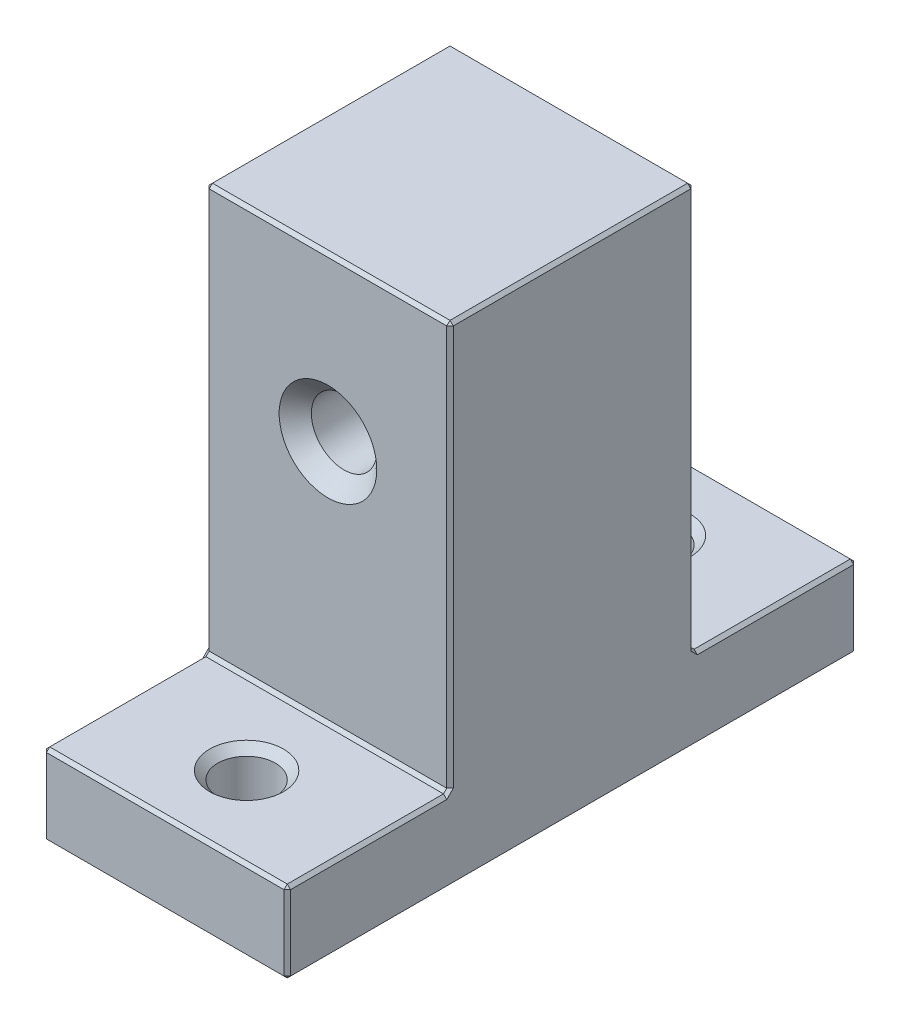
SolidWorks part; units mm, degrees
note: '?' marks a value the reader was unsure of. The reader was unsure of these and kept them because the rebuilt part matched: shared geometry of "Sketch1<3>".
material "6061-T6 (SS)"
ref_plane "Front Plane" through (0, 0, 0) normal (0, 0, 1) x (1, 0, 0)
ref_plane "Top Plane" through (0, 0, 0) normal (0, 1, 0) x (1, 0, 0)
ref_plane "Right Plane" through (0, 0, 0) normal (1, 0, 0) x (0, 0, -1)
ref_axis "X Axis" through (88.99, 0, 0) along (-1, 0, 0)?
ref_axis "Y Axis" through (0, 55, 0) along (0, -1, 0)?
ref_axis "Z Axis" through (0, 0, -88.99) along (0, 0, 1)?
sketch "Sketch1" plane through (0, 0, 0) normal (0, 1, 0) x (1, 0, 0)
  line L5 (-9.525, -22.225) -> (9.525, -22.225)
  line L6 (-9.525, -22.225) -> (-9.525, 22.225)
  line L11 (-9.525, 22.225) -> (9.525, 22.225)
  line L12 (9.525, -22.225) -> (9.525, 22.225)
  line L13 (0, 22.225) -> (0, -22.225) construction
  line L14 (-9.525, 0) -> (9.525, 0) construction
  line L15 (-9.525, -9.525) -> (9.525, -9.525)
  line L16 (-9.525, -9.525) -> (-9.525, 9.525)
  line L17 (-9.525, 9.525) -> (9.525, 9.525)
  line L18 (9.525, -9.525) -> (9.525, 9.525)
  line L19 (0, 9.525) -> (0, -9.525) construction
  line L20 (-9.525, 0) -> (9.525, 0) construction
  point P0 (0, 0)
  point P4 (0, 0)
  dimension "D1" = 19.05
  dimension "D2" = 19.05
  dimension "D3" = 44.45
extrude "Boss-Extrude1" add sketch "Sketch1" along normal blind 6.35 contours L5 L16 L11 L6 | L5 L18 L11 L16 | L18 L5 L12 L11
extrude "Boss-Extrude2" add sketch "Sketch1<3>" along normal blind 38.1 contours L5 L18 L11 L16
sketch "Sketch1<3>" plane through (0, 0, 0) normal (0, 1, 0) x (1, 0, 0) same geometry as "Sketch1"
sketch "Sketch3" plane through (0, 0, 9.525) normal (0, 0, 1) x (1, 0, 0)
  line L0 (0, 0) -> (0, 25.4) construction
  point P1 (0, 25.4)
  point P13 (0, 25.4)
  dimension "D1" = 25.4
hole_wizard "1/4-20 Tapped Hole1" positions "Sketch3" profile "Sketch4" tap size "1/4-20" standard "ANSI Inch" end condition through all
sketch "Sketch4" plane through (0, 25.4, 9.525) normal (1, 0, 0) x (0, -1, 0)
  line L0 (0, 0) -> (0, 19.05)
  line L1 (0, 19.05) -> (3.81, 19.05)
  line L2 (2.5527, 17.7927) -> (2.5527, 1.2573)
  line L3 (2.5527, 1.2573) -> (3.81, 0)
  line L5 (3.81, 0) -> (0, 0)
  line L6 (-2.5527, 1.2573) -> (-3.81, 0) construction
  line L7 (3.81, 19.05) -> (2.5527, 17.7927)
  line L8 (-3.81, 19.05) -> (-2.5527, 17.7927) construction
  line L11 (0, -6.35) -> (0, 107.95) construction
  dimension "Thru Tap Drill Dia." = 5.1054
  dimension "Thru Tap Drill Depth" = 19.05
  dimension "Near C'Sink Dia." = 7.62
  dimension "Near C'Sink Angle" = 90
  dimension "Far C'Sink Dia." = 7.62
  dimension "Far C'Sink Angle" = 90
cosmetic thread "Hole Thread1" parameters "D2"=6.35
sketch "Sketch6" plane through (0, 38.1, 0) normal (0, 1, 0) x (1, 0, 0)
  line L0 (0, -15.875) -> (0, 15.875)
  point P4 (0, 0)
  dimension "D1" = 31.75
sketch "Sketch9" plane through (0, 6.35, 0) normal (0, 1, 0) x (1, 0, 0)
  point P0 (0, 15.875)
  point P3 (0, -15.875)
hole_wizard "#8 Clearance Hole1" positions "Sketch9" profile "Sketch8" hole size "#8" standard "ANSI Inch" end condition through all
sketch "Sketch8" plane through (0, 6.35, -15.875) normal (1, 0, 0) x (0, 0, 1)
  line L0 (0, 0) -> (0, 6.35)
  line L1 (0, 6.35) -> (2.8829, 6.35)
  line L2 (2.2479, 5.715) -> (2.2479, 0.635)
  line L3 (2.2479, 0.635) -> (2.8829, 0)
  line L5 (2.8829, 0) -> (0, 0)
  line L6 (-2.2479, 0.635) -> (-2.8829, 0) construction
  line L7 (2.8829, 6.35) -> (2.2479, 5.715)
  line L8 (-2.8829, 6.35) -> (-2.2479, 5.715) construction
  line L11 (0, -6.35) -> (0, 107.95) construction
  dimension "Thru Hole Dia." = 4.4958
  dimension "Thru Hole Depth" = 6.35
  dimension "Near C'Sink Dia." = 5.7658
  dimension "Near C'Sink Angle" = 90
  dimension "Far C'Sink Dia." = 5.7658
  dimension "Far C'Sink Angle" = 90
chamfer "Chamfer1" distance 0.254 angle 45 24 edges at (-9.525, 38.1, 0) (9.525, 38.1, 0) (0, 38.1, 9.525) (0, 38.1, -9.525) (0, 0, 22.225) (0, 6.35, 22.225) (0, 0, -22.225) (0, 6.35, -22.225) (9.525, 3.175, -22.225) (9.525, 0, 0) (9.525, 3.175, 22.225) (9.525, 22.225, 9.525) (9.525, 22.225, -9.525) (-9.525, 22.225, -9.525) (-9.525, 22.225, 9.525) (0, 6.35, 9.525) (-9.525, 6.35, 15.875) (9.525, 6.35, 15.875) (-9.525, 3.175, 22.225) (-9.525, 0, 0) (-9.525, 3.175, -22.225) (0, 6.35, -9.525) (9.525, 6.35, -15.875) (-9.525, 6.35, -15.875)
ref_axis "Hole Axis" through (0, 25.4, -34.9674) along (0, 0, 1)?
